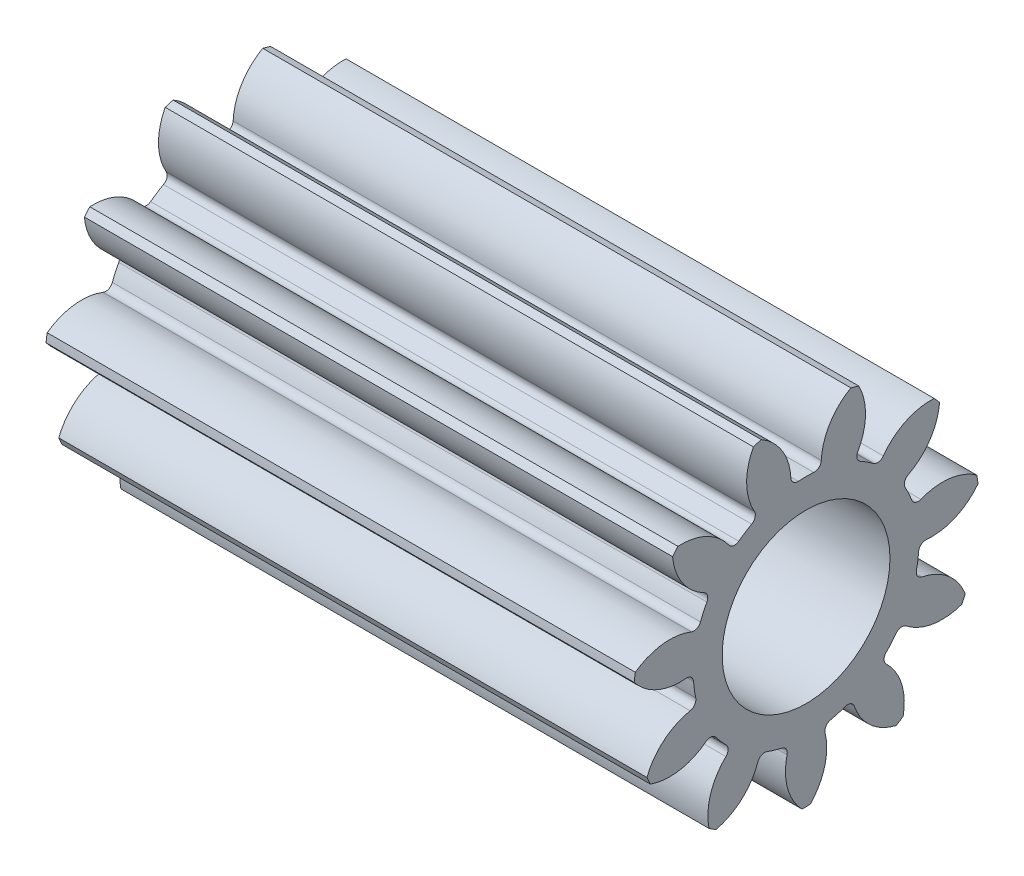
SolidWorks part; units mm, degrees
ref_plane "Plane1" through (0, 0, 0) normal (0, 0, 1) x (1, 0, 0)
ref_plane "Plane2" through (0, 0, 0) normal (0, 1, 0) x (1, 0, 0)
ref_plane "Plane3" through (0, 0, 0) normal (1, 0, 0) x (0, 0, -1)
other "Configuration Table"
sketch "HoldingSke" plane through (0, 0, 0) normal (0, 1, 0) x (1, 0, 0)
  line L0 (0, 0) -> (797.8666, -155.0896)
  line L1 (-15, 0) -> (100, 0) construction
  line L2 (0, 0) -> (-2.1039, 2.3779)
  line L3 (0, 0) -> (-11.863, 4.5341)
  line L4 (0, 0) -> (8.4773, 1.6478)
  line L5 (0, 0) -> (-47.5972, -17.7524)
  line L6 (0, 0) -> (-10.5278, -7.1032)
  line L7 (-2.1039, 2.3779) -> (8.8309, 51.9875)
  line L8 (-76.2, 54.61) -> (-75.184, 54.61)
  line L9 (-71.009, 38.7566) -> (-53.1078, 45.2721)
  line L10 (-76.2, 71.12) -> (104.1128, 71.12)
  line L11 (0, 0) -> (-12.7, 0)
  line L12 (-76.2, 101.6) -> (-76.1716, 101.6)
  line L13 (24.9733, 27.94) -> (52.9518, 28.4284)
  line L14 (24.9733, 27.94) -> (25.0241, 27.9398)
  line L15 (24.9733, 27.94) -> (100.4021, 29.52)
  circle A0 centre (0, 0) radius 0.3969
  circle A1 centre (0, 0) radius 3.3623
  circle A2 centre (0, 0) radius 38.1
  circle A3 centre (0, 0) radius 0.3969
  dimension "MHD" = 6.7246
  dimension "Hub_dia" = 76.2
  dimension "Bore" = 0.7937
  dimension "MBD" = 0.7937
  dimension "Num_teeth" = 11
  dimension "Pitch" = 812.8
  dimension "Overall_len" = 50.8
  dimension "Show_teeth" = 11
  dimension "Thickness" = 12.7
  dimension "OAL" = 50.8004
  dimension "T_dim" = 1.016
  dimension "Ap" = 20
  dimension "H" = 19.05
  dimension "Pitch_radius" = 180.3128
  dimension "Width" = 12.7
  dimension "Backlash" = 0.0284
  dimension "Addendum_fac" = 1
  dimension "Dedendum_fac" = 1.2
  dimension "Clearance_fac" = 0.2
  dimension "Dedendum_add" = 0.0508
sketch "BasProSke" plane through (0, 0, 0) normal (0, 1, 0) x (1, 0, 0)
  line L0 (-10, 0) -> (60, 0) construction
  line L1 (0, 0) -> (0, 5.1594)
  line L2 (0, 0) -> (17.526, 0)
  line L3 (17.526, 0) -> (17.526, 5.1594)
  line L4 (17.526, 5.1594) -> (0, 5.1594)
  dimension "Thickness" = 17.526
  dimension "Diameter" = 10.3187
revolve "Base-Revolve" add sketch "BasProSke" angle 360 about L0
sketch "TooCutSke" plane through (0, 0, 0) normal (1, 0, 0) x (0, 0, -1)
  line L1 (0, 0) -> (0, 107) construction
  line L2 (0, 0) -> (-0.671, 4.3138) construction
  line L3 (0, 0) -> (-2.4387, 8.3055) construction
  line L4 (-0.671, 4.3138) -> (-1.2194, 4.1527) construction
  arc A0 (0.4557, 3.3313) -> (-0.4557, 3.3313) centre (0, 0) ccw
  arc A1 (1.3674, 5.0012) -> (-1.3674, 5.0012) centre (0, 0) ccw
  circle A2 centre (0, 0) radius 4.3656 construction
  circle A3 centre (0, 0) radius 4.1023 construction
  arc A4 (-0.4557, 3.3313) -> (-1.3674, 5.0012) centre (-2.1969, 3.4645) ccw
  arc A5 (1.3674, 5.0012) -> (0.4557, 3.3313) centre (2.1969, 3.4645) ccw
  dimension "Root_dia" = 6.7246
  dimension "Overcut_dia" = 10.3696
  dimension "Pitch_dia" = 8.7312
  dimension "Base_dia" = 8.2047
  dimension "Flank_rad" = 1.7463
  dimension "Half_ang" = 16.364
  dimension "Half_CT" = 0.5715
extrude "ToothCut" cut sketch "TooCutSke" along normal through all
fillet "Breaks" [suppressed] radius 0.0159 tangent propagation no
fillet "RootFillets" radius 0.2095 2 edges at (8.763, 3.3313, -0.4557) (8.763, 3.3313, 0.4557)
pattern_circular "TeethCuts" count 11 every 32.727 about axis through (-10, 0, 0) along (1, 0, 0) of "ToothCut", "RootFillets", "Breaks"
sketch "HubNeaOneSke" plane through (0, 0, 0) normal (-1, 0, 0) x (0, 0, 1)
  circle A0 centre (0, 0) radius 3.3623
  dimension "Diameter" = 6.7246
extrude "HubNearOne" [suppressed] add sketch "HubNeaOneSke" along normal blind 33.2744
sketch "HubNeaBotSke" plane through (0, 0, 0) normal (-1, 0, 0) x (0, 0, 1)
  circle A0 centre (0, 0) radius 3.3623
  dimension "Diameter" = 6.7246
extrude "HubNearBoth" [suppressed] add sketch "HubNeaBotSke" along normal blind 16.6372
ref_plane "FarPln" through (17.526, 0, 0) normal (1, 0, 0) x (0, 0, -1)
sketch "HubFarSke" plane through (17.526, 0, 0) normal (1, 0, 0) x (0, 0, -1)
  circle A0 centre (0, 0) radius 3.3623
  dimension "Diameter" = 6.7246
extrude "HubFar" [suppressed] add sketch "HubFarSke" along normal blind 16.6372
sketch "BorSke" plane through (0, 0, 0) normal (1, 0, 0) x (0, 0, -1)
  circle A0 centre (0, 0) radius 0.3969
  dimension "Diameter" = 0.7937
extrude "Bore" [suppressed] cut sketch "BorSke" along normal mid plane 101.6008
sketch "KeySke" plane through (0, 0, 0) normal (1, 0, 0) x (0, 0, -1)
  line L0 (-0.127, 0) -> (-0.127, 0.6191)
  line L1 (-0.127, 0.6191) -> (0.127, 0.6191)
  line L2 (0.127, 0.6191) -> (0.127, 0)
  line L3 (0, 0) -> (0, 34) construction
  line L4 (-0.127, 0) -> (0.127, 0)
  dimension "Offset" = 0.6191
  dimension "Width" = 0.254
extrude "Keyway" [suppressed] cut sketch "KeySke" along normal mid plane 101.6008
pattern_circular "Keyway2" [suppressed] count 2 every 90 about axis through (-10, 0, 0) along (1, 0, 0) reverse direction yes
sketch "Sketch1" plane through (17.526, 0, 0) normal (1, 0, 0) x (0, 0, -1)
  circle A0 centre (0, 0) radius 2.5
  dimension "D1" = 5
extrude "Cut-Extrude1" cut sketch "Sketch1" against normal up to next
equation "' \"Pitch@HoldingSke\" = 4"
equation "' \"Num_teeth@HoldingSke\" = 12"
equation "' \"Ap@HoldingSke\" =  20"
equation "' \"Ap@HoldingSke\" = 20"
equation "' \"Width@HoldingSke\" = 0.5"
equation "' \"Hub_dia@HoldingSke\"= 1"
equation "' \"Hub_dia@HoldingSke\" = 1"
equation "' \"Overall_len@HoldingSke\" = 1.0"
equation "' \"Bore@HoldingSke\" = 0.75"
equation "' \"T_dim@HoldingSke\" = 0.85"
equation "' \"Width@KeySke\" = 0.25"
equation "' \"Show_teeth@HoldingSke\" = 13"
equation "' \"Backlash@HoldingSke\" = 0.009"
equation "' \"Addendum_fac@HoldingSke\" = 1.0"
equation "' \"Dedendum_fac@HoldingSke\" = 1.25"
equation "' \"Dedendum_add@HoldingSke\" = 0.00005"
equation "' \"Clearance_fac@HoldingSke\" = 0.25"
equation "' \"Pitch@HoldingSke\" = 0.5"
equation "' \"Num_teeth@HoldingSke\" = 23"
equation "' \"Show_teeth@HoldingSke\" = 23"
equation "' \"Backlash@HoldingSke\" = 0.0375"
equation "\"Overcut_dia@TooCutSke\" = (\"Num_teeth@HoldingSke\" + 2 * \"Addendum_fac@HoldingSke\") / \"Pitch@HoldingSke\" + 0.002"
equation "\"Pitch_dia@TooCutSke\" = \"Num_teeth@HoldingSke\" / \"Pitch@HoldingSke\""
equation "\"Base_dia@TooCutSke\" = \"Num_teeth@HoldingSke\" / \"Pitch@HoldingSke\" * cos((\"Ap@HoldingSke\"  * 3.14159265 / 180))"
equation "\"Root_dia@TooCutSke\" = (\"Num_teeth@HoldingSke\" + 2) / \"Pitch@HoldingSke\" - 2 * (\"Addendum_fac@HoldingSke\" + \"Dedendum_fac@HoldingSke\") / \"Pitch@HoldingSke\" - \"Dedendum_add@HoldingSke\" * 2"
equation "\"Half_ang@TooCutSke\" = 180 / \"Num_teeth@HoldingSke\""
equation "\"Half_CT@TooCutSke\" = \"Num_teeth@HoldingSke\" / \"Pitch@HoldingSke\" * sin((3.14159265 / 2 / \"Num_teeth@HoldingSke\")) / 2 - 7 * \"Backlash@HoldingSke\" / 4"
equation "\"Flank_rad@TooCutSke\" = \"Num_teeth@HoldingSke\" / \"Pitch@HoldingSke\" / 5"
equation "\"Radius@RootFillets\" = \"Clearance_fac@HoldingSke\" / \"Pitch@HoldingSke\" + \"Dedendum_add@HoldingSke\""
equation "\"Break_rad@Breaks\" = 0.02 / \"Pitch@HoldingSke\""
equation "\"Thickness@HoldingSke\" = \"Width@HoldingSke\""
equation "\"OAL@HoldingSke\" = \"Thickness@HoldingSke\""
equation "\"MHD@HoldingSke\" = (\"Num_teeth@HoldingSke\" + 2) / \"Pitch@HoldingSke\" - 2 * (\"Addendum_fac@HoldingSke\" + \"Dedendum_fac@HoldingSke\")  / \"Pitch@HoldingSke\" - \"Dedendum_add@HoldingSke\" * 2"
equation "\"MBD@HoldingSke\" = (\"Num_teeth@HoldingSke\" + 2) / \"Pitch@HoldingSke\" - 2 * (\"Addendum_fac@HoldingSke\" + \"Dedendum_fac@HoldingSke\")  / \"Pitch@HoldingSke\" - \"Dedendum_add@HoldingSke\" * 2 - 0.002"
equation "\"MHD@HoldingSke\" = ((sgn( \"MHD@HoldingSke\" - \"Hub_dia@HoldingSke\" )-1)*( \"MHD@HoldingSke\" - \"Hub_dia@HoldingSke\" ))/-2+ \"Hub_dia@HoldingSke\""
equation "\"MBD@HoldingSke\" = ((sgn( \"MBD@HoldingSke\" - \"Bore@HoldingSke\" )-1)*( \"MBD@HoldingSke\" - \"Bore@HoldingSke\" ))/-2+ \"Bore@HoldingSke\""
equation "\"OAL@HoldingSke\" = ((sgn( \"OAL@HoldingSke\" - \"Overall_len@HoldingSke\" )+1)*( \"OAL@HoldingSke\" - \"Overall_len@HoldingSke\" ))/2 + \"Overall_len@HoldingSke\" + 0.000002"
equation "\"Num_teeth@TeethCuts\" = int( \"Show_teeth@HoldingSke\" ) + 1"
equation "\"Num_teeth@TeethCuts\" = ((sgn( \"Num_teeth@TeethCuts\" - \"Num_teeth@HoldingSke\" )-1)*( \"Num_teeth@TeethCuts\" - \"Num_teeth@HoldingSke\" ))/-2+ \"Num_teeth@HoldingSke\""
equation "\"Num_teeth@TeethCuts\" = ((sgn( \"Num_teeth@TeethCuts\" - 2.0)+1)*( \"Num_teeth@TeethCuts\" - 2.0))/2 +2.0"
equation "\"Angle@TeethCuts\" = 360.0 / \"Num_teeth@HoldingSke\""
equation "\"Diameter@BasProSke\" = (\"Num_teeth@HoldingSke\" + 2 * \"Addendum_fac@HoldingSke\") / \"Pitch@HoldingSke\""
equation "\"Thickness@BasProSke\"=.69"
equation "' \"Fillet_rad@BasProSke\" =  \"Thickness@HoldingSke\" * 0.05"
equation "' \"Fillet_rad@BasProSke\" = \"Thickness@HoldingSke\" * 0.05"
equation "\"MHD@HoldingSke\" = ((sgn( \"MHD@HoldingSke\" - \"Root_dia@TooCutSke\" )-1)*( \"MHD@HoldingSke\" - \"Root_dia@TooCutSke\" ))/-2+ \"Root_dia@TooCutSke\""
equation "\"Diameter@HubNeaOneSke\" = \"MHD@HoldingSke\""
equation "\"Length@HubNearOne\" = \"OAL@HoldingSke\" - \"Thickness@BasProSke\""
equation "\"Diameter@HubNeaBotSke\" = \"MHD@HoldingSke\""
equation "\"Length@HubNearBoth\" = ( \"OAL@HoldingSke\" - \"Thickness@BasProSke\" ) / 2.0"
equation "\"Thickness@FarPln\" = \"Thickness@BasProSke\""
equation "\"Diameter@HubFarSke\" = \"MHD@HoldingSke\""
equation "\"Length@HubFar\" = ( \"OAL@HoldingSke\" - \"Thickness@BasProSke\" ) / 2.0"
equation "\"Diameter@BorSke\" = \"MBD@HoldingSke\""
equation "\"D1@Bore\" = \"OAL@HoldingSke\" * 2.0"
equation "\"D1@Keyway\" = \"OAL@HoldingSke\" * 2.0"
equation "\"Offset@KeySke\" = \"T_dim@HoldingSke\" - \"MBD@HoldingSke\" / 2.0"
equation "\"D1@Sketch1\"=5mm"
